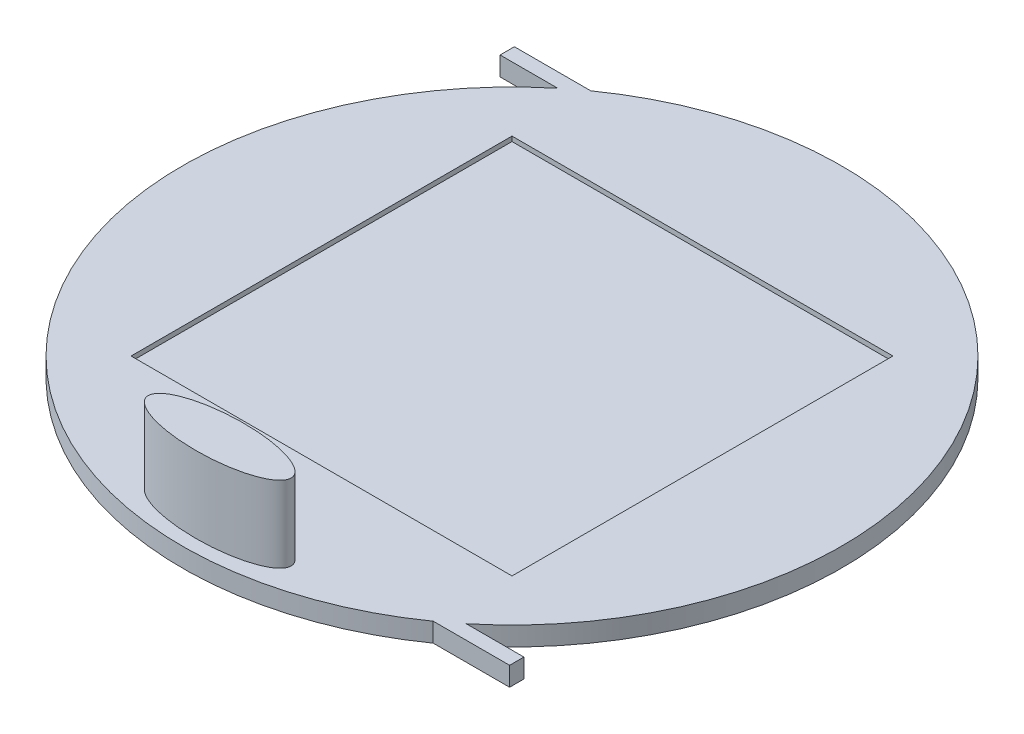
SolidWorks part; units mm, degrees
ref_plane "Front Plane" through (0, 0, 0) normal (0, 0, 1) x (1, 0, 0)
ref_plane "Top Plane" through (0, 0, 0) normal (0, 1, 0) x (1, 0, 0)
ref_plane "Right Plane" through (0, 0, 0) normal (1, 0, 0) x (0, 0, -1)
sketch "Sketch1" plane through (0, 0, 0) normal (0, 1, 0) x (1, 0, 0)
  line L0 (-2.5, -2) -> (2.5, -2) construction
  line L1 (2.5, -2) -> (0, 5) construction
  line L2 (0, 5) -> (-2.5, -2) construction
  line L3 (0, 0) -> (0, -2) construction
  line L4 (0, 5.7433) -> (-2.8548, -2.25)
  line L5 (-2.8548, -2.25) -> (2.8548, -2.25)
  line L6 (2.8548, -2.25) -> (0, 5.7433)
  line L7 (-32.9646, 10.5116) -> (-32.9646, -10.5116)
  line L8 (0, 27.5) -> (0, -27.5) construction
  line L9 (0, 27.5) -> (-28, 27.5)
  line L10 (0, -27.5) -> (28, -27.5)
  circle A0 centre (0, 0) radius 35 construction
  circle A1 centre (0, 0) radius 34.6
  dimension "D1" = 70
  dimension "D3" = 7
  dimension "D4" = 5
  dimension "D5" = 2
  dimension "D7" = 55
  dimension "D8" = 28
  dimension "D2" = 0.4
  dimension "D6" = 0.25
extrude "Boss-Extrude1" add sketch "Sketch1" along normal blind 2 contours L5 L6 L4 | A1 L6 L5 L4 | L7 A1 region at (0, 0, -0.4144) region at (-27.4961, 0, -19.3684) region at (-33.6201, 0, 0)
sketch "Sketch3" plane through (0, 2, 0) normal (0, 1, 0) x (1, 0, 0)
  line L0 (-7.5, -30.6947) -> (7.5, -30.6947) construction
  ellipse E0 centre (0, -30.6947) end of major axis (7.5, -30.6947) minor radius 2.5
  dimension "D1" = 5
  dimension "D2" = 15
extrude "Boss-Extrude2" add sketch "Sketch3" along normal blind 8
sketch "Sketch4" plane through (0, 2, 0) normal (0, 1, 0) x (1, 0, 0)
  line L1 (-20, 20) -> (20, 20)
  line L2 (-20, 20) -> (-20, -20)
  line L3 (-20, -20) -> (20, -20)
  line L4 (20, 20) -> (20, -20)
  line L5 (-20, 20) -> (20, -20) construction
  line L6 (-20, -20) -> (20, 20) construction
  point P0 (0, 0)
  dimension "D1" = 40
extrude "Cut-Extrude3" cut sketch "Sketch4" against normal blind 0.5
sketch "Sketch7" plane through (0, 0, 0) normal (0, 0, 1) x (1, 0, 0)
  line L0 (-34.6, 1) -> (-29.75, 0)
  line L1 (-34.6, 2) -> (-34.6, 0) construction
  line L2 (-34.6, 0) -> (34.6, 0) construction
  line L3 (-29.75, 0) -> (-34.6, 0)
  line L4 (-34.6, 0) -> (-34.6, 1)
extrude "Cut-Extrude4" cut sketch "Sketch7" against normal blind 21 and the other way blind 22 contours L3 L4 L0
extrude "Extrude-Thin1" add sketch "Sketch1<6>" along normal blind 2 thin contours L9 | L10 thin type mid plane wall 1.5
sketch "Sketch1<6>" plane through (0, 0, 0) normal (0, 1, 0) x (1, 0, 0) same geometry as "Sketch1"
sketch "Sketch8" [suppressed] plane through (0, 2, 0) normal (0, 1, 0) x (1, 0, 0)
  line L1 (-16.5, 7) -> (16.5, 7)
  line L2 (-16.5, 7) -> (-16.5, -7)
  line L3 (-16.5, -7) -> (16.5, -7)
  line L4 (16.5, 7) -> (16.5, -7)
  line L5 (-16.5, 7) -> (16.5, -7) construction
  line L6 (-16.5, -7) -> (16.5, 7) construction
  point P0 (0, 0)
  dimension "D1" = 33
  dimension "D2" = 14
extrude "Boss-Extrude3" [suppressed] add sketch "Sketch8" along normal blind 10
